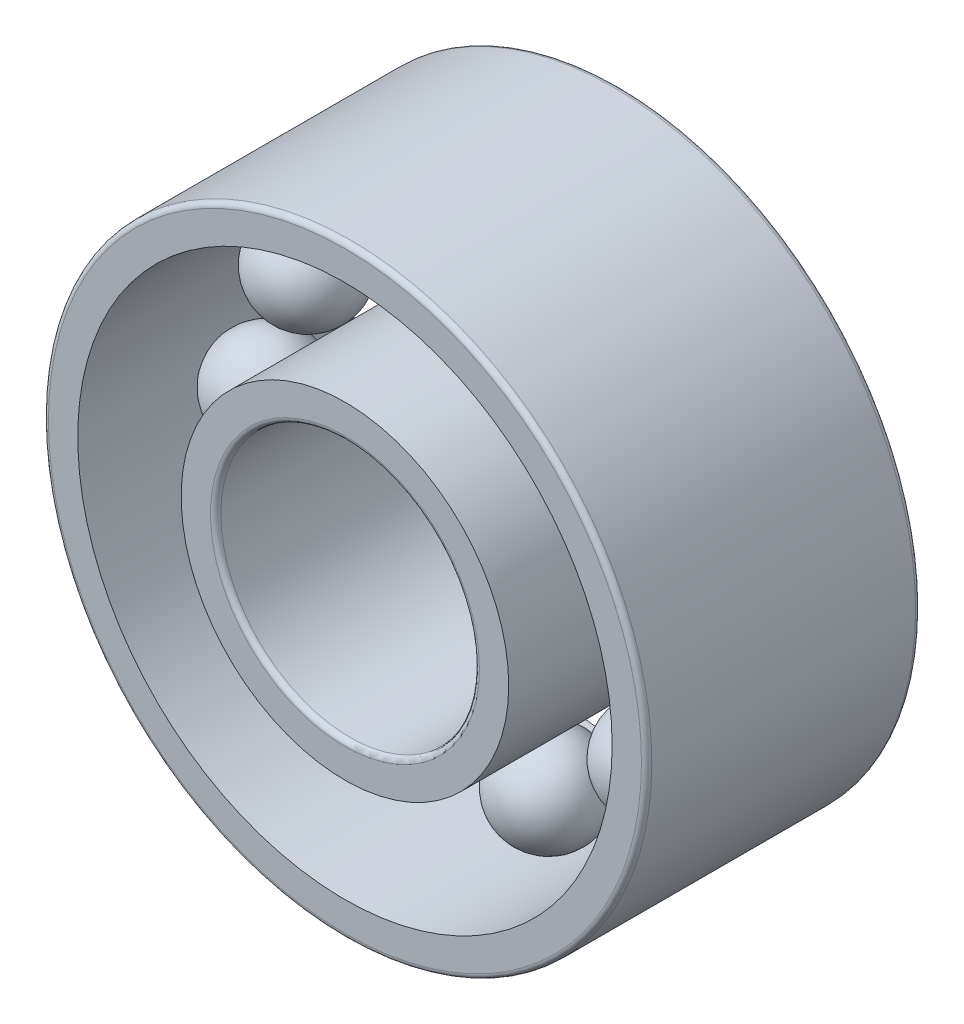
SolidWorks part; units mm, degrees
ref_plane "Front Plane" through (0, 0, 0) normal (0, 0, 1) x (1, 0, 0)
ref_plane "Top Plane" through (0, 0, 0) normal (0, 1, 0) x (1, 0, 0)
ref_plane "Right Plane" through (0, 0, 0) normal (1, 0, 0) x (0, 0, -1)
sketch "S" plane through (0, 0, 0) normal (0, 0, 1) x (1, 0, 0)
  line L0 (-7.95, 0) -> (7.95, 0) construction
  circle A0 centre (0, 0) radius 7.5 construction
  circle A1 centre (0, 0) radius 17.5 construction
  circle A2 centre (0, 0) radius 9.5 construction
  circle A3 centre (0, 0) radius 15.5 construction
  dimension "ID" = 15
  dimension "OD" = 35
  dimension "IDa" = 19
  dimension "ODa" = 31
  dimension "B" = 15.9
ref_axis "Z" through (0, 0, -8.745) along (0, 0, 1)
sketch "InnerS" plane through (0, 0, 0) normal (0, 1, 0) x (1, 0, 0)
  line L0 (7.5, -7.95) -> (9.5, -7.95)
  line L1 (9.5, -7.95) -> (9.5, 7.95)
  line L2 (9.5, 7.95) -> (7.5, 7.95)
  line L3 (7.5, 7.95) -> (7.5, -7.95)
  line L4 (0, -12.925) -> (0, 12.925) construction
  dimension "r1" = 7.5
  dimension "r2" = 9.5
  dimension "z1" = 7.95
  dimension "z2" = 7.95
revolve "InnerRing" add sketch "InnerS" angle 360 about L4
sketch "OuterS" plane through (0, 0, 0) normal (0, 1, 0) x (1, 0, 0)
  line L0 (15.5, -7.95) -> (17.5, -7.95)
  line L1 (17.5, -7.95) -> (17.5, 7.95)
  line L2 (17.5, 7.95) -> (15.5, 7.95)
  line L3 (15.5, 7.95) -> (15.5, -7.95)
  line L4 (0, -12.925) -> (0, 12.925) construction
  dimension "r1" = 15.5
  dimension "r2" = 17.5
  dimension "z1" = 7.95
  dimension "z2" = 7.95
revolve "OuterRing" add sketch "OuterS" angle 360 about L4
sketch "BallS" plane through (0, 0, 0) normal (0, 1, 0) x (1, 0, 0)
  line L0 (9.65, 0) -> (15.35, 0)
  arc A0 (9.65, 0) -> (15.35, 0) centre (12.5, 0) ccw
  dimension "r" = 2.85
  dimension "p" = 12.5
revolve "Ball" add sketch "BallS" angle 360 about L0
pattern_circular "BallsPattern" count 10 over 360 about axis through (0, 0, -8.745) along (0, 0, 1) of bodies 103
fillet "F1" radius 0.3 2 edges at (17.5, 0, -7.95) (17.5, 0, 7.95)
fillet "F2" radius 0.3 2 edges at (7.5, 0, -7.95) (7.5, 0, 7.95)
equation "\"r1@InnerS\" = abs(0.5*\"ID@S\")"
equation "\"r2@InnerS\" = abs(0.5*\"IDa@S\")"
equation "\"z1@InnerS\" = abs(-0.5*\"B@S\")"
equation "\"z2@InnerS\" = abs(0.5*\"B@S\")"
equation "\"r1@OuterS\" = abs(0.5*\"ODa@S\")"
equation "\"r2@OuterS\" = abs(0.5*\"OD@S\")"
equation "\"z1@OuterS\" = abs(-0.5*\"B@S\")"
equation "\"z2@OuterS\" = abs(0.5*\"B@S\")"
equation "\"r@BallS\" = abs(0.2375*\"ODa@S\"-0.2375*\"IDa@S\")"
equation "\"p@BallS\" = abs(0.25*\"IDa@S\"+0.25*\"ODa@S\")"
equation "\"N@BallsPattern\" = int(2.417*(0.25*\"IDa@S\"+0.25*\"ODa@S\")/(0.2375*\"ODa@S\"-0.2375*\"IDa@S\"))"
equation "\"r_min@F2\" = \"r_min@F1\""
